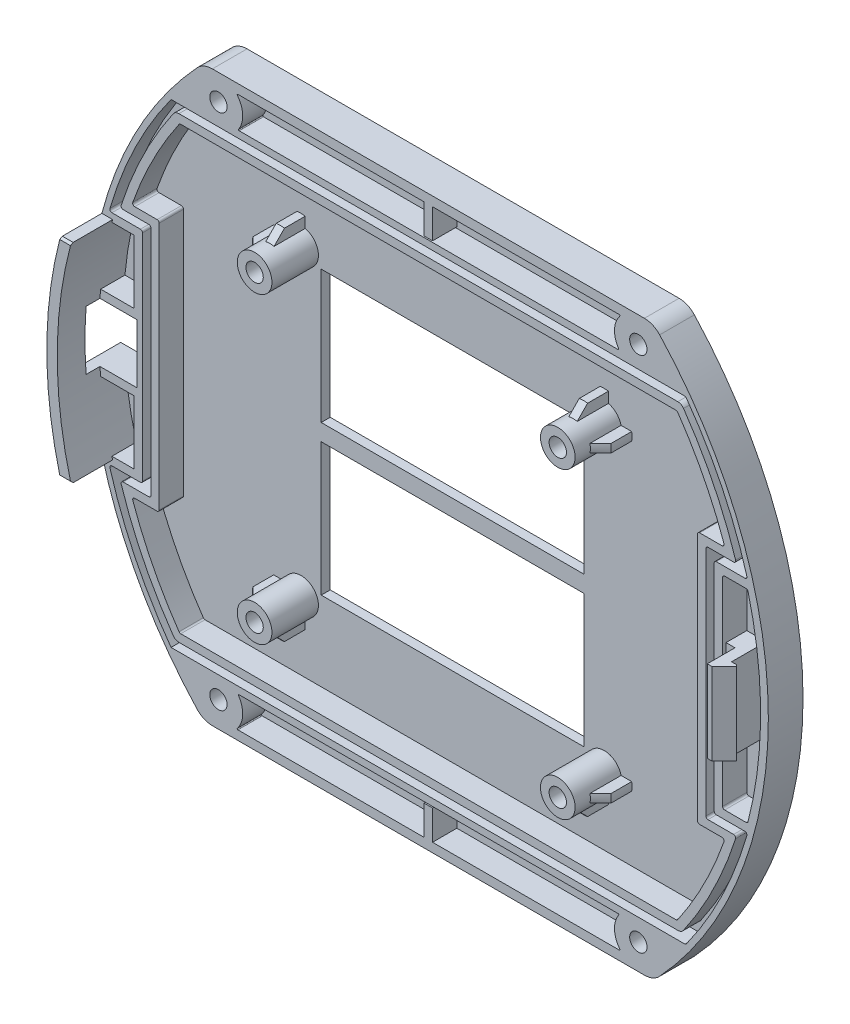
SolidWorks part; units mm, degrees
ref_plane "Front Plane" through (0, 0, 0) normal (0, 0, 1) x (1, 0, 0)
ref_plane "Top Plane" through (0, 0, 0) normal (0, 1, 0) x (1, 0, 0)
ref_plane "Right Plane" through (0, 0, 0) normal (1, 0, 0) x (0, 0, -1)
sketch "Sketch1" plane through (0, 0, 0) normal (0, 0, 1) x (1, 0, 0)
  line L0 (0, 35) -> (0, -35) construction
  line L7 (-37.5, -35) -> (37.5, -35)
  line L8 (37.5, 35) -> (-37.5, 35)
  line L10 (37.5, 35) -> (37.5, -35) construction
  line L11 (-37.5, 35) -> (-37.5, -35) construction
  arc A4 (-37.5, 35) -> (-37.5, -35) centre (10, 0) ccw
  arc A5 (37.5, 35) -> (37.5, -35) centre (-10, 0) cw
  point P17 (10, 0)
  dimension "D2" = 75
extrude "Boss-Extrude1" add sketch "Sketch1" along normal blind 5
sketch "Sketch2" plane through (0, 0, 5) normal (0, 0, 1) x (1, 0, 0)
  line L0 (-49.0021, 0) -> (49.0021, 0) construction
  line L1 (-42.635, 0) -> (-42.635, -15) construction
  line L2 (-42.635, 0) -> (-42.635, 15) construction
  line L3 (-45.5112, 15) -> (-47.0636, 15)
  line L4 (-45.5112, -15) -> (-47.0636, -15)
  arc A0 (-37.5, 35) -> (-37.5, -35) centre (10, 0) ccw construction
  arc A1 (37.5, -35) -> (37.5, 35) centre (-10, 0) ccw construction
  arc A2 (-47.0636, 15) -> (-47.0636, -15) centre (10, 0) ccw
  arc A4 (-36.2924, 34.1102) -> (-36.2924, -34.1102) centre (10, 0) ccw
  arc A5 (-45.5112, 15) -> (-45.5112, -15) centre (10, 0) ccw
  dimension "D1" = 15
  dimension "D2" = 15
  dimension "D3" = 1.5
extrude "Boss-Extrude2" add sketch "Sketch2" along normal blind 6
ref_plane "Plane2" through (-42, 0, 0) normal (1, 0, 0) x (0, 0, -1)
sketch "Sketch6" plane through (-42, 0, 0) normal (1, 0, 0) x (0, 0, -1)
  line L0 (0, 0) -> (-11, 0) construction
  line L1 (-11, 15) -> (-11, -15) construction
  line L2 (-11, 0) -> (-7, 0) construction
  line L3 (-7, 0) -> (-7, 4.25)
  line L4 (-7, 0) -> (-7, -4.25)
  line L5 (-7, 4.25) -> (0, 4.25)
  line L6 (0, -35) -> (0, 35) construction
  line L7 (0, 4.25) -> (0, -4.25)
  line L8 (0, -4.25) -> (-7, -4.25)
  dimension "D1" = 4
  dimension "D2" = 4.25
  dimension "D3" = 4.25
extrude "Cut-Extrude2" cut sketch "Sketch6" against normal blind 8
sketch "Sketch8" plane through (0, 0, 5) normal (0, 0, 1) x (1, 0, 0)
  line L0 (0, 0) -> (0, 35) construction
  line L1 (37.5, 35) -> (-37.5, 35) construction
  line L2 (0, 35) -> (0, -35) construction
  line L3 (-37.5, -35) -> (37.5, -35) construction
  line L4 (0, 0) -> (49.0021, 0) construction
  line L5 (0, 0) -> (42, 0) construction
  line L6 (42, 0) -> (44, 0) construction
  line L13 (0, 0) -> (43.2, 0) construction
  line L14 (43.7, -5.9) -> (45.2, -5.9)
  line L15 (45.2, -5.9) -> (45.2, 5.9)
  line L16 (45.2, 5.9) -> (43.7, 5.9)
  line L19 (45.2, 5.9) -> (43.7, 5.9) construction
  line L20 (43.7, 5.9) -> (43.7, -5.9)
  arc A0 (37.5, -35) -> (37.5, 35) centre (-10, 0) ccw construction
  point P5 (45.2, 0)
  dimension "D1" = 42
  dimension "D2" = 2
  dimension "D3" = 11.8
  dimension "D5" = 1.5
  dimension "D6" = 43.2
extrude "Boss-Extrude4" add sketch "Sketch8" along normal blind 3.5
ref_plane "Plane3" through (0, 0, 6.5) normal (0, 0, 1) x (1, 0, 0)
sketch "Sketch9" plane through (0, 0, 6.5) normal (0, 0, 1) x (1, 0, 0)
  line L0 (45.2, 5.9) -> (46.4, 5.9)
  line L1 (46.4, 5.9) -> (46.4, -5.9)
  line L2 (46.4, -5.9) -> (45.2, -5.9)
  line L3 (45.2, 5.9) -> (45.2, -5.9)
  dimension "D1" = 1.2
extrude "Boss-Extrude5" add sketch "Sketch9" along normal blind 2
chamfer "Chamfer2" distance 2 angle 45 1 edges at (46.4, 0, 8.5)
chamfer "Chamfer3" distance 0.5 angle 45 1 edges at (46.4, 0, 6.5)
sketch "Sketch10" plane through (0, 0, 0) normal (0, 0, 1) x (1, 0, 0)
  line L0 (-32.4294, 41) -> (32.4294, 41)
  line L1 (-37.5, 35) -> (37.5, 35)
  line L2 (-32.4294, -41) -> (32.4294, -41)
  line L3 (-37.5, -35) -> (37.5, -35)
  line L4 (0, 41) -> (0, -41) construction
  line L5 (-10, 0) -> (10, 0) construction
  arc A0 (-37.5, 35) -> (-32.4294, 41) centre (10, 0) cw
  arc A1 (37.5, 35) -> (32.4294, 41) centre (-10, 0) ccw
  arc A2 (-37.5, -35) -> (-32.4294, -41) centre (10, 0) ccw
  arc A3 (37.5, -35) -> (32.4294, -41) centre (-10, 0) cw
extrude "Boss-Extrude6" add sketch "Sketch10" along normal blind 5
sketch "Sketch11" plane through (0, 0, 5) normal (0, 0, 1) x (1, 0, 0)
  line L0 (-41.2021, 0) -> (42.0021, 0) construction
  line L1 (0, 41) -> (0, -41) construction
  circle A0 centre (-30.2641, -37.3072) radius 1.25
  circle A1 centre (30.2641, -37.3072) radius 1.25
  circle A2 centre (30.2641, 37.3072) radius 1.25
  circle A3 centre (-30.2641, 37.3072) radius 1.25
extrude "Cut-Extrude3" cut sketch "Sketch11" against normal blind 5
sketch "Sketch12" plane through (0, 0, 0) normal (0, 0, -1) x (-1, 0, 0)
  circle A0 centre (-30.2641, 37.3072) radius 3
  circle A1 centre (30.2641, 37.3072) radius 3
  circle A2 centre (30.2641, -37.3072) radius 3
  circle A3 centre (-30.2641, -37.3072) radius 3
  dimension "D1" = 6
  dimension "D2" = 6
  dimension "D3" = 6
  dimension "D4" = 6
extrude "Cut-Extrude4" cut sketch "Sketch12" against normal blind 2.5
sketch "Sketch13" plane through (0, 0, 5) normal (0, 0, 1) x (1, 0, 0)
  line L0 (-46.0165, 15.8) -> (-41.2021, 15.8)
  line L1 (-41.2021, 15.8) -> (-41.2021, -15.8)
  line L2 (-41.2021, -15.8) -> (-46.0165, -15.8)
  line L3 (-37.094, -34.2) -> (37.094, -34.2)
  line L4 (46.0165, -15.8) -> (41.2021, -15.8)
  line L5 (41.2021, -15.8) -> (41.2021, 15.8)
  line L6 (41.2021, 15.8) -> (46.0165, 15.8)
  line L7 (37.094, 34.2) -> (-37.094, 34.2)
  line L8 (10, 0) -> (-10, 0) construction
  line L9 (0, 34.2) -> (0, -34.2) construction
  line L10 (-44.4081, 17) -> (-40.0021, 17)
  line L11 (-35.9591, 33) -> (35.9591, 33)
  line L12 (-40.0021, 17) -> (-40.0021, -17)
  line L13 (44.4081, 17) -> (40.0021, 17)
  line L14 (40.0021, 17) -> (40.0021, -17)
  line L15 (44.4081, -17) -> (40.0021, -17)
  line L16 (-35.9591, -33) -> (35.9591, -33)
  line L17 (-44.4081, -17) -> (-40.0021, -17)
  line L18 (0, 33) -> (0, -33) construction
  arc A0 (-37.094, 34.2) -> (-46.0165, 15.8) centre (10, 0) ccw
  arc A1 (-46.0165, -15.8) -> (-37.094, -34.2) centre (10, 0) ccw
  arc A2 (37.094, -34.2) -> (46.0165, -15.8) centre (-10, 0) ccw
  arc A3 (46.0165, 15.8) -> (37.094, 34.2) centre (-10, 0) ccw
  arc A4 (-36.7797, 32.5714) -> (-44.4081, 17) centre (10, 0) ccw
  arc A5 (-36.7797, 32.5714) -> (-35.9591, 33) centre (-35.9591, 32) cw
  arc A6 (36.7797, 32.5714) -> (35.9591, 33) centre (35.9591, 32) ccw
  arc A7 (36.7797, 32.5714) -> (44.4081, 17) centre (-10, 0) cw
  arc A8 (36.7797, -32.5714) -> (44.4081, -17) centre (-10, 0) ccw
  arc A9 (36.7797, -32.5714) -> (35.9591, -33) centre (35.9591, -32) cw
  arc A10 (-36.7797, -32.5714) -> (-35.9591, -33) centre (-35.9591, -32) ccw
  arc A11 (-36.7797, -32.5714) -> (-44.4081, -17) centre (10, 0) cw
  point P23 (0, 33)
  point P28 (40.0021, 0)
  point P42 (-40.0021, 0)
extrude "Cut-Extrude6" cut sketch "Sketch13" against normal blind 2.5
sketch "Sketch14" plane through (0, 0, 5) normal (0, 0, 1) x (1, 0, 0)
  line L16 (-42.7507, 18.2) -> (-38.8021, 18.2)
  line L17 (-38.8021, 18.2) -> (-38.8021, -18.2)
  line L18 (-38.8021, -18.2) -> (-42.7507, -18.2)
  line L19 (-35.8545, -31.8) -> (35.8545, -31.8)
  line L20 (42.7507, -18.2) -> (38.8021, -18.2)
  line L21 (38.8021, -18.2) -> (38.8021, 18.2)
  line L22 (38.8021, 18.2) -> (42.7507, 18.2)
  line L23 (35.8545, 31.8) -> (-35.8545, 31.8)
  line L24 (-42.7507, 18.2) -> (-38.8021, 18.2)
  line L25 (-38.8021, 18.2) -> (-38.8021, -18.2)
  line L26 (-38.8021, -18.2) -> (-42.7507, -18.2)
  line L27 (-35.8545, -31.8) -> (35.8545, -31.8)
  line L28 (42.7507, -18.2) -> (38.8021, -18.2)
  line L29 (38.8021, -18.2) -> (38.8021, 18.2)
  line L30 (38.8021, 18.2) -> (42.7507, 18.2)
  line L31 (35.8545, 31.8) -> (-35.8545, 31.8)
  arc A16 (-35.8545, 31.8) -> (-42.7507, 18.2) centre (10, 0) ccw
  arc A17 (-42.7507, -18.2) -> (-35.8545, -31.8) centre (10, 0) ccw
  arc A18 (35.8545, -31.8) -> (42.7507, -18.2) centre (-10, 0) ccw
  arc A19 (42.7507, 18.2) -> (35.8545, 31.8) centre (-10, 0) ccw
  arc A20 (-35.8545, 31.8) -> (-42.7507, 18.2) centre (10, 0) ccw
  arc A21 (-42.7507, -18.2) -> (-35.8545, -31.8) centre (10, 0) ccw
  arc A22 (35.8545, -31.8) -> (42.7507, -18.2) centre (-10, 0) ccw
  arc A23 (42.7507, 18.2) -> (35.8545, 31.8) centre (-10, 0) ccw
  dimension "D1" = 1.2
extrude "Cut-Extrude7" cut sketch "Sketch14" against normal blind 3.5
sketch "Sketch15" plane through (0, 0, 5) normal (0, 0, 1) x (1, 0, 0)
  line L0 (0.031, 41) -> (0.031, -41) construction
  line L1 (-40.0021, -0.0076) -> (42.0021, -0.0076) construction
  line L2 (27.5192, -39.6767) -> (-27.4573, -39.6767)
  line L3 (-27.2755, 35.2002) -> (27.3374, 35.2002)
  line L4 (-27.2831, -35.2042) -> (27.345, -35.2042)
  line L5 (27.5155, 39.6568) -> (-27.4535, 39.6568)
  arc A12 (-27.5316, 39.4943) -> (-27.3585, 35.356) centre (-30.2641, 37.3072) cw
  arc A13 (27.5935, 39.4943) -> (27.4204, 35.356) centre (30.326, 37.3072) ccw
  arc A14 (27.5972, -39.5141) -> (27.4278, -35.3603) centre (30.326, -37.3225) cw
  arc A15 (-27.5352, -39.5141) -> (-27.3659, -35.3603) centre (-30.2641, -37.3225) ccw
  arc A16 (-27.2755, 35.2002) -> (-27.3585, 35.356) centre (-27.2755, 35.3002) cw
  arc A17 (-27.5316, 39.4943) -> (-27.4535, 39.6568) centre (-27.4535, 39.5568) cw
  arc A18 (27.4278, -35.3603) -> (27.345, -35.2042) centre (27.345, -35.3042) ccw
  arc A19 (27.3374, 35.2002) -> (27.4204, 35.356) centre (27.3374, 35.3002) ccw
  arc A20 (27.5935, 39.4943) -> (27.5155, 39.6568) centre (27.5155, 39.5568) ccw
  arc A21 (27.5192, -39.6767) -> (27.5972, -39.5141) centre (27.5192, -39.5767) ccw
  arc A22 (-27.3659, -35.3603) -> (-27.2831, -35.2042) centre (-27.2831, -35.3042) cw
  arc A23 (-27.5352, -39.5141) -> (-27.4573, -39.6767) centre (-27.4573, -39.5767) ccw
  point P14 (0.031, -39.6767)
  point P20 (0.031, -35.2042)
  dimension "D1" = 3.5
  dimension "D2" = 0.1
  dimension "D3" = 0.1
  dimension "D4" = 0.1
  dimension "D5" = 0.1
  dimension "D6" = 0.1
extrude "Cut-Extrude8" cut sketch "Sketch15" against normal blind 3.5
sketch "Sketch16" plane through (0, 0, 5) normal (0, 0, 1) x (1, 0, 0)
  line L2 (42.4021, -15.8) -> (42.4021, 15.8)
  line L3 (42.4021, -14.6) -> (42.4021, 14.6)
  line L5 (41.2021, 14.6) -> (46.0165, 14.6)
  line L6 (42.4021, 14.6) -> (46.0165, 14.6)
  line L8 (46.0165, -14.6) -> (41.2021, -14.6)
  line L9 (46.0165, -14.6) -> (42.4021, -14.6)
  line L19 (43.7, 5.9) -> (45.2, 5.9)
  line L20 (45.2, 5.9) -> (43.7, 5.9) construction
  line L21 (45.2, 5.9) -> (45.2, -5.9)
  line L22 (45.2, -5.9) -> (43.7, -5.9)
  line L23 (43.7, -5.9) -> (43.7, 5.9)
  arc A0 (46.0165, -14.6) -> (46.0165, 14.6) centre (-10, 0) ccw
  arc A1 (46.0165, 15.8) -> (37.094, 34.2) centre (-10, 0) ccw construction
  dimension "D1" = 1.2
  dimension "D2" = 1.2
  dimension "D3" = 1.2
extrude "Cut-Extrude10" cut sketch "Sketch16" against normal blind 3.5
sketch "Sketch17" plane through (0, 0, 1.5) normal (0, 0, 1) x (1, 0, 0)
  line L0 (43.7, 5.9) -> (42.4021, 5.9)
  line L1 (42.4021, 14.6) -> (42.4021, -14.6) construction
  line L2 (42.4021, 5.9) -> (42.4021, -5.9)
  line L3 (42.4021, 14.6) -> (42.4021, -14.6) construction
  line L4 (42.4021, -5.9) -> (43.7, -5.9)
  line L5 (43.7, -5.9) -> (43.7, 5.9)
extrude "Boss-Extrude7" add sketch "Sketch17" along normal blind 3
sketch "Sketch19" plane through (0, 0, 1.5) normal (0, 0, 1) x (1, 0, 0)
  line L0 (0, -39.8) -> (0, 39.8) construction
  line L1 (-41.2021, 0) -> (41.2021, -0.15) construction
  line L2 (0.6, -35.4) -> (0.6, -39.8)
  line L3 (0.6, -39.8) -> (-0.6, -39.8)
  line L4 (-0.6, -39.8) -> (-0.6, -35.4)
  line L5 (-0.6, -35.4) -> (0.6, -35.4)
  line L6 (-0.6, 35.4) -> (-0.6, 39.8)
  line L7 (-0.6, 39.8) -> (0.6, 39.8)
  line L8 (0.6, 39.8) -> (0.6, 35.4)
  line L9 (0.6, 35.4) -> (-0.6, 35.4)
extrude "Boss-Extrude8" add sketch "Sketch19" along normal blind 3.5
chamfer "Chamfer4" distance 0.3 angle 45 1 edges at (-46.2874, -15, 11)
chamfer "Chamfer5" distance 0.3 angle 45 1 edges at (-46.2874, 15, 11)
chamfer "Chamfer8" distance 0.5 angle 45 2 edges at (-45.4244, 4.25, 0) (-45.4244, -4.25, 0)
sketch "Sketch21" plane through (0, 0, 5) normal (0, 0, 1) x (1, 0, 0)
  line L2 (-41.2021, -14.6) -> (-46.0165, -14.6)
  line L3 (-42.4021, -14.6) -> (-45.6177, -14.6)
  line L5 (-47.3448, -5.45) -> (-42, -5.45)
  line L6 (-47.2433, -5.45) -> (-42.4021, -5.45)
  line L8 (-42.4021, 15.8) -> (-42.4021, -15.8)
  line L9 (-42.4021, 14.6) -> (-42.4021, 5.45)
  line L11 (-42, 5.45) -> (-47.3448, 5.45)
  line L12 (-42.4021, 5.45) -> (-47.2433, 5.45)
  line L13 (-42.4021, -5.45) -> (-42.4021, -14.6)
  line L14 (-46.0165, 14.6) -> (-41.2021, 14.6)
  line L15 (-45.6177, 14.6) -> (-42.4021, 14.6)
  arc A2 (-47.3448, -4.25) -> (-45.5112, -15) centre (10, 0) ccw
  arc A3 (-47.2433, -5.45) -> (-45.6177, -14.6) centre (10, 0) ccw
  arc A5 (-45.5112, 15) -> (-47.3448, 4.25) centre (10, 0) ccw
  arc A6 (-45.6177, 14.6) -> (-47.2433, 5.45) centre (10, 0) ccw
  dimension "D1" = 0
  dimension "D2" = 0
  dimension "D3" = 1.2
  dimension "D4" = 1.2
  dimension "D5" = 1.2
  dimension "D6" = 1.2
  dimension "D7" = 1.2
extrude "Cut-Extrude11" cut sketch "Sketch21" against normal blind 3.5
sketch "Sketch22" plane through (0, 0, 1.5) normal (0, 0, 1) x (1, 0, 0)
  line L0 (-38.8021, 0) -> (38.8021, 0) construction
  line L1 (-21.85, 21.85) -> (-21.85, -21.85) construction
  line L2 (-21.85, -21.85) -> (21.85, -21.85) construction
  line L3 (-38.8021, 18.2) -> (-38.8021, -18.2) construction
  line L4 (38.8021, -18.2) -> (38.8021, 18.2) construction
  line L5 (0, 31.8) -> (0, -31.8) construction
  line L6 (35.8545, 31.8) -> (-35.8545, 31.8) construction
  line L7 (-35.8545, -31.8) -> (35.8545, -31.8) construction
  circle A0 centre (-21.85, 21.85) radius 1.25
  circle A1 centre (-21.85, 21.85) radius 2.5
  circle A2 centre (-21.85, -21.85) radius 1.25
  circle A3 centre (-21.85, -21.85) radius 2.5
  circle A4 centre (21.85, -21.85) radius 1.25
  circle A5 centre (21.85, -21.85) radius 2.5
  circle A6 centre (21.85, 21.85) radius 2.5
  circle A7 centre (21.85, 21.85) radius 1.25
  point P14 (-21.85, 0)
  point P16 (0, -21.85)
  dimension "D3" = 2.5
  dimension "D4" = 5
  dimension "D5" = 2.5
  dimension "D6" = 5
  dimension "D1" = 43.7
  dimension "D2" = 43.7
extrude "Boss-Extrude9" add sketch "Sketch22" along normal blind 6.7
sketch "Sketch23" plane through (0, 0, 1.5) normal (0, 0, 1) x (1, 0, 0)
  line L0 (0, 31.8) -> (0, -31.8) construction
  line L1 (35.8545, 31.8) -> (-35.8545, 31.8) construction
  line L2 (-35.8545, -31.8) -> (35.8545, -31.8) construction
  line L3 (-38.8021, 0) -> (38.8021, 0) construction
  line L4 (-38.8021, 18.2) -> (-38.8021, -18.2) construction
  line L5 (38.8021, -18.2) -> (38.8021, 18.2) construction
  line L6 (-21.85, 21.85) -> (-21.85, 26.4502) construction
  line L7 (-21.25, 24.2769) -> (-21.25, 25.8047)
  line L8 (-22.45, 24.2769) -> (-22.45, 25.8047)
  line L9 (-21.85, 21.85) -> (-26.9377, 21.85) construction
  line L10 (-22.45, 21.85) -> (-22.45, 26.4502) construction
  line L11 (-21.25, 21.85) -> (-21.25, 26.4502) construction
  line L12 (-21.85, 21.85) -> (-25.1057, 25.1057) construction
  line L13 (-24.2769, 22.45) -> (-25.8047, 22.45)
  line L14 (-24.2769, 21.25) -> (-25.8047, 21.25)
  line L15 (-24.2769, -21.25) -> (-25.8047, -21.25)
  line L16 (-24.2769, -22.45) -> (-25.8047, -22.45)
  line L17 (-22.45, -24.2769) -> (-22.45, -25.8047)
  line L18 (-21.25, -24.2769) -> (-21.25, -25.8047)
  line L19 (21.25, -24.2769) -> (21.25, -25.8047)
  line L20 (22.45, -24.2769) -> (22.45, -25.8047)
  line L21 (24.2769, -22.45) -> (25.8047, -22.45)
  line L22 (24.2769, -21.25) -> (25.8047, -21.25)
  line L23 (24.2769, 21.25) -> (25.8047, 21.25)
  line L24 (24.2769, 22.45) -> (25.8047, 22.45)
  line L25 (22.45, 24.2769) -> (22.45, 25.8047)
  line L26 (21.25, 24.2769) -> (21.25, 25.8047)
  arc A0 (-21.25, 24.2769) -> (-22.45, 24.2769) centre (-21.85, 21.85) ccw
  arc A3 (-22.45, 25.8047) -> (-21.25, 25.8047) centre (-21.85, 21.85) cw
  arc A4 (-24.2769, 21.25) -> (-24.2769, 22.45) centre (-21.85, 21.85) cw
  arc A5 (-25.8047, 22.45) -> (-25.8047, 21.25) centre (-21.85, 21.85) ccw
  arc A6 (-25.8047, -22.45) -> (-25.8047, -21.25) centre (-21.85, -21.85) cw
  arc A7 (-24.2769, -21.25) -> (-24.2769, -22.45) centre (-21.85, -21.85) ccw
  arc A8 (-21.25, -24.2769) -> (-22.45, -24.2769) centre (-21.85, -21.85) cw
  arc A9 (-22.45, -25.8047) -> (-21.25, -25.8047) centre (-21.85, -21.85) ccw
  arc A10 (22.45, -25.8047) -> (21.25, -25.8047) centre (21.85, -21.85) cw
  arc A11 (21.25, -24.2769) -> (22.45, -24.2769) centre (21.85, -21.85) ccw
  arc A12 (24.2769, -21.25) -> (24.2769, -22.45) centre (21.85, -21.85) cw
  arc A13 (25.8047, -22.45) -> (25.8047, -21.25) centre (21.85, -21.85) ccw
  arc A14 (25.8047, 22.45) -> (25.8047, 21.25) centre (21.85, 21.85) cw
  arc A15 (24.2769, 21.25) -> (24.2769, 22.45) centre (21.85, 21.85) ccw
  arc A16 (21.25, 24.2769) -> (22.45, 24.2769) centre (21.85, 21.85) cw
  arc A17 (22.45, 25.8047) -> (21.25, 25.8047) centre (21.85, 21.85) ccw
  dimension "D1" = 1.5
  dimension "D4" = 45
  dimension "D2" = 0.6
  dimension "D3" = 0.6
extrude "Boss-Extrude10" add sketch "Sketch23" along normal blind 5
chamfer "Chamfer9" distance 2 angle 45 8 edges at (-25.85, 21.85, 6.5) (-21.85, 25.85, 6.5) (21.85, 25.85, 6.5) (25.85, 21.85, 6.5) (25.85, -21.85, 6.5) (21.85, -25.85, 6.5) (-21.85, -25.85, 6.5) (-25.85, -21.85, 6.5)
sketch "Sketch24" plane through (0, 0, 1.5) normal (0, 0, 1) x (1, 0, 0)
  line L0 (-21.85, -21.85) -> (21.85, -21.85) construction
  line L1 (21.85, -21.85) -> (21.85, 21.85) construction
  line L2 (21.85, 21.85) -> (-21.85, 21.85) construction
  line L3 (-21.85, 21.85) -> (-21.85, -21.85) construction
  line L4 (0, -21.85) -> (0, 21.85) construction
  line L5 (-21.85, 0) -> (21.85, 0) construction
  line L6 (21.85, 20.35) -> (-21.85, 20.35) construction
  line L7 (18.95, -21.85) -> (18.95, 21.85) construction
  line L8 (-21.85, -20.35) -> (21.85, -20.35) construction
  line L9 (-21.85, -1.2) -> (21.85, -1.2) construction
  line L10 (-18.95, -21.85) -> (-18.95, 21.85) construction
  line L11 (-21.85, 1.2) -> (21.85, 1.2) construction
  line L12 (0, -1.2) -> (-18.95, -1.2)
  line L13 (-18.95, -1.2) -> (-18.95, -20.35)
  line L14 (-18.95, -20.35) -> (18.95, -20.35)
  line L15 (18.95, -20.35) -> (18.95, -1.2)
  line L16 (18.95, -1.2) -> (0, -1.2)
  line L18 (-18.95, 1.2) -> (-18.95, 20.35)
  line L19 (-18.95, 20.35) -> (18.95, 20.35)
  line L20 (18.95, 20.35) -> (18.95, 1.2)
  line L21 (18.95, 1.2) -> (-18.95, 1.2)
  dimension "D1" = 1.5
  dimension "D2" = 2.9
  dimension "D3" = 1.5
  dimension "D4" = 1.2
  dimension "D5" = 1.2
extrude "Cut-Extrude12" cut sketch "Sketch24" against normal blind 1.5
sketch "Sketch26" plane through (0, 0, 0) normal (0, 0, -1) x (-1, 0, 0)
  line L0 (0, 41) -> (0, -41) construction
  line L1 (-32.4294, 41) -> (32.4294, 41) construction
  line L2 (32.4294, -41) -> (-32.4294, -41) construction
  line L3 (-49.0021, 0) -> (42, 0) construction
  line L4 (42, -4.75) -> (42, 4.75) construction
  line L5 (0, 0) -> (0, 25) construction
  line L6 (0, 25) -> (-25, 25)
  line L7 (0, 25) -> (25, 25)
  line L8 (-25, 25) -> (-25, -25)
  line L9 (-25, -25) -> (25, -25)
  line L10 (25, -25) -> (25, 25)
  arc A0 (-32.4294, 41) -> (-32.4294, -41) centre (10, 0) ccw construction
  dimension "D1" = 25
  dimension "D2" = 25
  dimension "D3" = 25
  dimension "D4" = 50
  dimension "D5" = 50
extrude "Cut-Extrude13" cut sketch "Sketch26" against normal blind 0.2
fillet "Fillet1" radius 2 1 edges at (25, 25, 0.1)
fillet "Fillet2" radius 2 1 edges at (-25, 25, 0.1)
fillet "Fillet3" radius 2 1 edges at (-25, -25, 0.1)
fillet "Fillet4" radius 2 1 edges at (25, -25, 0.1)
fillet "Fillet5" radius 3 4 edges at (-32.4294, 41, 2.5) (-32.4294, -41, 2.5) (32.4294, -41, 2.5) (32.4294, 41, 2.5)
fillet "Fillet6" radius 0.3 1 edges at (-44.4081, -17, 3.75)
fillet "Fillet7" radius 0.3 1 edges at (-46.0165, -15.8, 3.75)
fillet "Fillet8" radius 0.3 1 edges at (-41.2021, -15.8, 3.75)
fillet "Fillet9" radius 0.3 1 edges at (-40.0021, -17, 3.75)
fillet "Fillet10" radius 0.3 1 edges at (-40.0021, 17, 3.75)
fillet "Fillet11" radius 0.3 1 edges at (-41.2021, 15.8, 3.75)
fillet "Fillet13" radius 0.3 1 edges at (-46.0165, 15.8, 3.75)
fillet "Fillet14" radius 0.3 1 edges at (-44.4081, 17, 3.75)
fillet "Fillet15" radius 0.3 1 edges at (-42.7507, 18.2, 3.25)
fillet "Fillet16" radius 0.3 1 edges at (-38.8021, 18.2, 3.25)
fillet "Fillet17" radius 0.3 1 edges at (-35.8545, 31.8, 3.25)
fillet "Fillet18" radius 0.3 1 edges at (-38.8021, -18.2, 3.25)
fillet "Fillet19" radius 0.3 1 edges at (-42.7507, -18.2, 3.25)
fillet "Fillet20" radius 0.3 1 edges at (-35.8545, -31.8, 3.25)
fillet "Fillet21" radius 0.3 1 edges at (35.8545, -31.8, 3.25)
fillet "Fillet22" radius 0.3 2 edges at (38.8021, -18.2, 3.25) (42.7507, -18.2, 3.25)
fillet "Fillet23" radius 0.3 1 edges at (44.4081, -17, 3.75)
fillet "Fillet24" radius 0.3 1 edges at (40.0021, -17, 3.75)
fillet "Fillet26" radius 0.3 1 edges at (38.8021, 18.2, 3.25)
fillet "Fillet27" radius 0.3 1 edges at (41.2021, 15.8, 3.75)
fillet "Fillet28" radius 0.3 1 edges at (42.7507, 18.2, 3.25)
fillet "Fillet29" radius 0.3 1 edges at (40.0021, 17, 3.75)
fillet "Fillet30" radius 0.3 1 edges at (44.4081, 17, 3.75)
fillet "Fillet31" radius 0.3 1 edges at (35.8545, 31.8, 3.25)
fillet "Fillet32" radius 0.3 1 edges at (46.0165, 15.8, 3.75)
fillet "Fillet33" radius 0.3 1 edges at (46.0165, -15.8, 3.75)
fillet "Fillet34" radius 0.3 1 edges at (41.2021, -15.8, 3.75)
fillet "Fillet35" radius 0.3 1 edges at (42.4021, -14.6, 3.25)
fillet "Fillet36" radius 0.3 1 edges at (46.0165, -14.6, 3.25)
fillet "Fillet37" radius 0.3 1 edges at (42.4021, 14.6, 3.25)
fillet "Fillet38" radius 0.3 1 edges at (46.0165, 14.6, 3.25)
fillet "Fillet39" radius 0.3 1 edges at (37.094, -34.2, 3.75)
fillet "Fillet40" radius 0.3 1 edges at (37.094, 34.2, 3.75)
fillet "Fillet42" radius 0.5 1 edges at (-33.2641, -37.3072, 0)
fillet "Fillet43" radius 0.5 1 edges at (-33.2641, 37.3072, 0)
fillet "Fillet44" radius 0.5 1 edges at (27.2641, 37.3072, 0)
fillet "Fillet45" radius 0.5 1 edges at (27.2641, -37.3072, 0)
sketch "Sketch27" plane through (0, 0, 8.2) normal (0, 0, 1) x (1, 0, 0)
  circle A0 centre (-21.85, 21.85) radius 1.25
